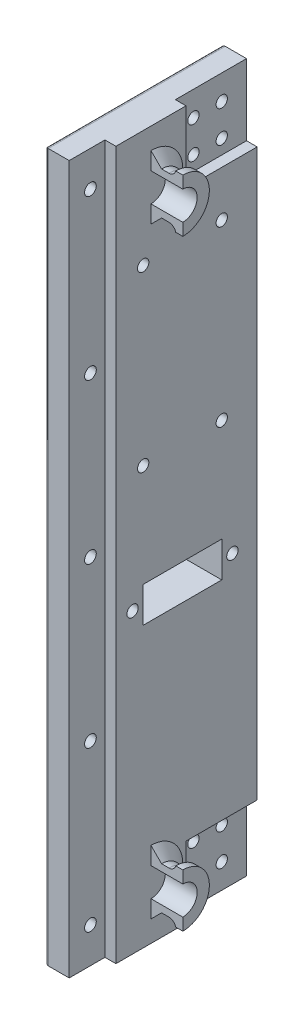
SolidWorks part; units mm, degrees
ref_plane "Front Plane" through (0, 0, 0) normal (0, 0, 1) x (1, 0, 0)
ref_plane "Top Plane" through (0, 0, 0) normal (0, 1, 0) x (1, 0, 0)
ref_plane "Right Plane" through (0, 0, 0) normal (1, 0, 0) x (0, 0, -1)
sketch "Sketch2" plane through (0, 0, 0) normal (1, 0, 0) x (0, 0, -1)
  line L1 (-40.827, 121.3238) -> (9.173, 121.3238)
  line L2 (-40.827, 121.3238) -> (-40.827, -78.6762)
  line L3 (-40.827, -78.6762) -> (9.173, -78.6762)
  line L4 (9.173, 121.3238) -> (9.173, -78.6762)
  dimension "D1" = 200
  dimension "D2" = 50
extrude "Boss-Extrude2" add sketch "Sketch2" along normal blind 10
sketch "Sketch4" plane through (10, 0, 0) normal (1, 0, 0) x (0, 0, -1)
  line L0 (-40.827, 121.3238) -> (-40.827, -78.6762) construction
  line L1 (9.173, 121.3238) -> (-40.827, 121.3238) construction
  line L2 (-40.827, -78.6762) -> (9.173, -78.6762) construction
  circle A0 centre (-20.827, 106.3238) radius 6
  circle A1 centre (-20.827, -63.6762) radius 6
  dimension "D1" = 12
  dimension "D2" = 20
  dimension "D3" = 15
  dimension "D4" = 12
  dimension "D5" = 20
  dimension "D6" = 15
extrude "Boss-Extrude3" add sketch "Sketch4" along normal blind 7
sketch "Sketch5" plane through (17, 0, 0) normal (1, 0, 0) x (0, 0, -1)
  circle A0 centre (-20.827, -63.6762) radius 7.5
  circle A1 centre (-20.827, 106.3238) radius 7.5
  dimension "D1" = 15
  dimension "D2" = 15
extrude "Boss-Extrude4" add sketch "Sketch5" along normal blind 2
sketch "Sketch8" plane through (10, 0, 0) normal (1, 0, 0) x (0, 0, -1)
  line L0 (-40.827, -78.6762) -> (9.173, -78.6762) construction
  line L1 (-10.927, -78.6762) -> (9.173, -78.6762)
  line L2 (-10.927, -78.6762) -> (-10.927, -58.5762)
  line L3 (-10.927, -58.5762) -> (9.173, -58.5762)
  line L4 (9.173, -78.6762) -> (9.173, -58.5762)
  line L5 (9.173, -78.6762) -> (9.173, 121.3238) construction
  line L6 (9.173, 121.3238) -> (-40.827, 121.3238) construction
  line L7 (-10.927, 121.3238) -> (9.173, 121.3238)
  line L8 (-10.927, 121.3238) -> (-10.927, 101.2238)
  line L9 (-10.927, 101.2238) -> (9.173, 101.2238)
  line L10 (9.173, 121.3238) -> (9.173, 101.2238)
  dimension "D1" = 20.1
  dimension "D2" = 20.1
  dimension "D3" = 20.1
  dimension "D4" = 20.1
extrude "Cut-Extrude4" cut sketch "Sketch8" against normal blind 3
sketch "Sketch9" plane through (7, 0, 0) normal (1, 0, 0) x (0, 0, -1)
  line L0 (-10.927, -78.6762) -> (9.173, -78.6762) construction
  line L1 (-10.927, -58.5762) -> (-10.927, -78.6762) construction
  line L2 (9.173, -58.5762) -> (-10.927, -58.5762) construction
  line L3 (9.173, -78.6762) -> (9.173, -58.5762) construction
  line L4 (9.173, 121.3238) -> (-10.927, 121.3238) construction
  line L5 (-10.927, 121.3238) -> (-10.927, 101.2238) construction
  line L6 (9.173, 101.2238) -> (9.173, 121.3238) construction
  line L7 (-10.927, 101.2238) -> (9.173, 101.2238) construction
  circle A1 centre (-5.827, 114.3238) radius 1.6
  circle A2 centre (2.173, 105.3238) radius 1.6
  circle A3 centre (2.173, 114.3238) radius 1.6
  circle A4 centre (-5.827, -71.6762) radius 1.6
  circle A6 centre (2.173, -62.6762) radius 1.6
  circle A7 centre (2.173, -71.6762) radius 1.6
  dimension "D1" = 3.2
  dimension "D3" = 3.2
  dimension "D4" = 3.2
  dimension "D6" = 3.2
  dimension "D7" = 3.2
  dimension "D8" = 3.2
  dimension "D9" = 7
  dimension "D10" = 5.1
  dimension "D13" = 4.1
  dimension "D14" = 7
  dimension "D15" = 7
  dimension "D16" = 7
  dimension "D17" = 7
  dimension "D18" = 5.1
  dimension "D19" = 7
  dimension "D20" = 7
  dimension "D21" = 7
  dimension "D22" = 4.1
extrude "Cut-Extrude5" cut sketch "Sketch9" against normal through all
sketch "Sketch10" plane through (19, 0, 0) normal (1, 0, 0) x (0, 0, -1)
  line L0 (-40.827, 121.3238) -> (-40.827, -78.6762) construction
  line L1 (-20.827, -74.8141) -> (-40.827, -74.8141)
  line L2 (-20.827, -74.8141) -> (-20.827, -51.4007)
  line L3 (-20.827, -51.4007) -> (-40.827, -51.4007)
  line L4 (-40.827, -74.8141) -> (-40.827, -51.4007)
  line L6 (-20.827, 95.0015) -> (-40.827, 95.0015)
  line L7 (-20.827, 95.0015) -> (-20.827, 115.0728)
  line L8 (-20.827, 115.0728) -> (-40.827, 115.0728)
  line L9 (-40.827, 95.0015) -> (-40.827, 115.0728)
  dimension "D1" = 20
  dimension "D2" = 20
extrude "Cut-Extrude8" cut sketch "Sketch10" against normal up to surface (9 mm away) up to face at (10, 21.3238, 13.377)
sketch "Sketch11" plane through (19, 0, 0) normal (1, 0, 0) x (0, 0, -1)
  line L0 (-20.827, -71.1762) -> (-20.827, -56.1762) construction
  line L1 (-20.827, 98.8238) -> (-20.827, 113.8238) construction
  circle A0 centre (-20.827, -63.6762) radius 4.05
  circle A1 centre (-20.827, 106.3238) radius 4.05
  dimension "D1" = 8.1
  dimension "D2" = 8.1
extrude "Cut-Extrude9" cut sketch "Sketch11" against normal up to surface (9 mm away) up to face at (10, -63.6762, 17.827)
sketch "Sketch12" plane through (10, 0, 0) normal (1, 0, 0) x (0, 0, -1)
  circle A0 centre (-23.027, 39.3238) radius 1.6
  circle A1 centre (-23.027, 88.3238) radius 1.6
  circle A2 centre (-0.827, 88.3238) radius 1.6
  circle A3 centre (-0.827, 39.3238) radius 1.6
  dimension "D1" = 3.2
  dimension "D2" = 3.2
  dimension "D3" = 3.2
  dimension "D4" = 3.2
extrude "Cut-Extrude10" cut sketch "Sketch12" against normal through all
fillet "Fillet2" radius 2 2 edges at (17, 106.3238, 14.827) (17, -63.6762, 14.827)
fillet "Fillet3" radius 1 4 edges at (0, 121.3238, 15.827) (0, 21.3238, -9.173) (0, -78.6762, 15.827) (0, 21.3238, 40.827)
chamfer "Chamfer1" distance 3 angle 45 2 edges at (10, 106.3238, 14.827) (10, -63.6762, 14.827)
sketch "Sketch14" plane through (0, 0, 0) normal (-1, 0, 0) x (0, 0, 1)
  line L0 (-9.173, 121.3238) -> (40.827, 121.3238) construction
  line L1 (40.827, -78.6762) -> (-9.173, -78.6762) construction
  line L2 (40.827, 121.3238) -> (40.827, -78.6762) construction
  circle A0 centre (34.827, 111.3238) radius 1.65
  circle A1 centre (34.827, 66.3238) radius 1.65
  circle A2 centre (34.827, 21.3238) radius 1.65
  circle A3 centre (34.827, -23.6762) radius 1.65
  circle A4 centre (34.827, -68.6762) radius 1.65
  dimension "D1" = 3.3
  dimension "D2" = 3.3
  dimension "D3" = 3.3
  dimension "D4" = 3.3
  dimension "D5" = 3.3
  dimension "D6" = 10
  dimension "D7" = 10
  dimension "D8" = 45
  dimension "D9" = 45
  dimension "D10" = 45
  dimension "D11" = 6
  dimension "D12" = 6
  dimension "D13" = 6
  dimension "D14" = 6
  dimension "D15" = 6
extrude "Cut-Extrude12" cut sketch "Sketch14" against normal through all
sketch "Sketch15" plane through (0, -78.6762, 0) normal (0, -1, 0) x (1, 0, 0)
  line L1 (10, 40.827) -> (6.9, 40.827)
  line L2 (10, 40.827) -> (10, 30.727)
  line L3 (10, 30.727) -> (6.9, 30.727)
  line L4 (6.9, 40.827) -> (6.9, 30.727)
  dimension "D1" = 3.1
  dimension "D2" = 10.1
extrude "Cut-Extrude13" cut sketch "Sketch15" against normal through all
sketch "Sketch16" plane through (10, 0, 0) normal (1, 0, 0) x (0, 0, -1)
  line L0 (-30.727, -78.6762) -> (-10.927, -78.6762) construction
  line L1 (-23.027, 0.2738) -> (-0.827, 0.2738)
  line L2 (-23.027, 0.2738) -> (-23.027, 10.2738)
  line L3 (-23.027, 10.2738) -> (-0.827, 10.2738)
  line L4 (-0.827, 0.2738) -> (-0.827, 10.2738)
  line L5 (9.173, -58.5762) -> (9.173, 101.2238) construction
  dimension "D1" = 88.95
  dimension "D2" = 10
  dimension "D3" = 10
  dimension "D4" = 22.2
extrude "Cut-Extrude14" cut sketch "Sketch16" against normal blind 10
sketch "Sketch17" plane through (0, 0, 0) normal (-1, 0, 0) x (0, 0, 1)
  line L0 (0.827, 0.2738) -> (0.827, 10.2738) construction
  line L1 (23.027, 10.2738) -> (23.027, 0.2738) construction
  line L2 (23.027, 0.2738) -> (0.827, 0.2738) construction
  circle A0 centre (26.027, 5.2738) radius 1.6
  circle A1 centre (-2.173, 5.2738) radius 1.6
  dimension "D1" = 3.2
  dimension "D2" = 3
  dimension "D3" = 3.2
  dimension "D4" = 3
  dimension "D5" = 5
  dimension "D6" = 5
extrude "Cut-Extrude15" cut sketch "Sketch17" against normal through all
sketch "Sketch18" plane through (7, 0, 0) normal (1, 0, 0) x (0, 0, -1)
  line L0 (-10.927, -58.5762) -> (-10.927, -78.6762) construction
  line L1 (9.173, -58.5762) -> (-10.927, -58.5762) construction
  circle A0 centre (-5.827, -62.6762) radius 1.6
  dimension "D1" = 3.2
  dimension "D2" = 5.1
  dimension "D3" = 4.1
extrude "Cut-Extrude16" cut sketch "Sketch18" against normal through all
sketch "Sketch19" plane through (7, 0, 0) normal (1, 0, 0) x (0, 0, -1)
  line L0 (-10.927, 121.3238) -> (-10.927, 101.2238) construction
  line L1 (-10.927, 101.2238) -> (9.173, 101.2238) construction
  circle A0 centre (-5.827, 105.3238) radius 1.6
  dimension "D1" = 3.2
  dimension "D2" = 5.1
  dimension "D3" = 4.1
extrude "Cut-Extrude17" cut sketch "Sketch19" against normal through all
